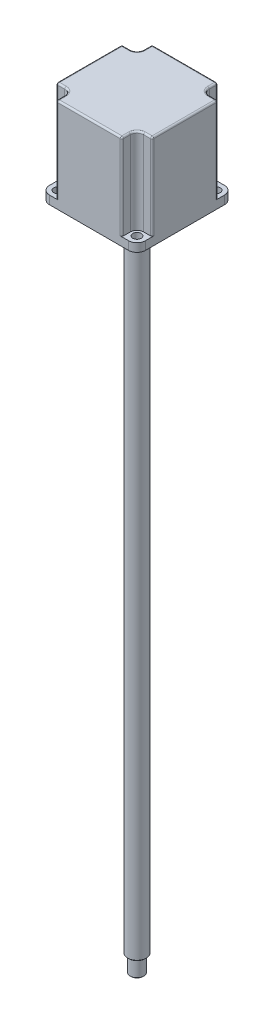
SolidWorks part; units mm, degrees
note: '?' marks a value the reader was unsure of.
material "1023 Carbon Steel Sheet (SS)"
ref_plane "Front" through (0, 0, 0) normal (0, 0, 1) x (1, 0, 0)
ref_plane "Top" through (0, 0, 0) normal (0, 1, 0) x (1, 0, 0)
ref_plane "Right" through (0, 0, 0) normal (1, 0, 0) x (0, 0, -1)
ref_axis "Axis1" through (-84.4107, 0, 0) along (1, 0, 0)?
ref_axis "Axis2" through (0, 64.3378, 0) along (0, -1, 0)?
ref_axis "Axis3" through (0, 0, -102.329) along (0, 0, 1)?
sketch "Sketch1" plane through (0, 0, 0) normal (0, 1, 0) x (1, 0, 0)
  line L1 (-28.5, -28.5) -> (28.5, -28.5)
  line L2 (-28.5, -28.5) -> (-28.5, 28.5)
  line L3 (-28.5, 28.5) -> (28.5, 28.5)
  line L4 (28.5, -28.5) -> (28.5, 28.5)
  line L5 (-28.5, -28.5) -> (28.5, 28.5) construction
  line L6 (-28.5, 28.5) -> (28.5, -28.5) construction
  point P0 (0, 0)
  dimension "D1" = 57
  dimension "D2" = 57
extrude "Extrude1" add sketch "Sketch1" along normal blind 76
hole_wizard "Ø5.0 (5) Diameter Hole1" positions "Sketch5" profile "Sketch4" hole size "Ø5.0" standard "ISO" end condition through all
sketch "Sketch5" plane through (0, 0, 0) normal (0, -1, 0) x (1, 0, 0)
  line L0 (-28.5, 28.5) -> (28.5, -28.5) construction
  line L3 (28.5, 28.5) -> (-28.5, -28.5) construction
  point P0 (-23.5, 23.5)
  point P1 (23.5, 23.5)
  point P3 (23.5, -23.5)
  point P5 (-23.5, -23.5)
  dimension "D1" = 47
  dimension "D2" = 47
sketch "Sketch4" plane through (-23.5, 0, 23.5) normal (1, 0, 0) x (0, 0, -1)
  line L0 (0, 0) -> (0, 76)
  line L1 (0, 76) -> (2.5, 76)
  line L2 (2.5, 76) -> (2.5, 0)
  line L5 (2.5, 0) -> (0, 0)
  line L11 (0, -6.35) -> (0, 107.95) construction
  dimension "Thru Hole Dia." = 5
  dimension "Thru Hole Depth" = 76
sketch "Sketch6" plane through (0, 76, 0) normal (0, 1, 0) x (1, 0, 0)
  line L0 (-19.5, 23.5) -> (-19.5, 32.5117)
  line L1 (-19.5, 32.5117) -> (-33.9089, 32.5117)
  line L2 (-33.9089, 32.5117) -> (-33.9089, 19.5)
  line L3 (-33.9089, 19.5) -> (-23.5, 19.5)
  line L4 (19.5, 23.5) -> (19.5, 36.4716)
  line L5 (19.5, 36.4716) -> (41.1684, 36.4716)
  line L6 (41.1684, 36.4716) -> (41.1684, 19.5)
  line L7 (41.1684, 19.5) -> (23.5, 19.5)
  line L8 (23.5, -19.5) -> (44.2522, -19.5)
  line L9 (44.2522, -19.5) -> (44.2522, -40.0504)
  line L10 (44.2522, -40.0504) -> (19.5, -40.0504)
  line L11 (19.5, -40.0504) -> (19.5, -23.5)
  line L12 (-23.5, -19.5) -> (-37.6708, -19.5)
  line L13 (-37.6708, -19.5) -> (-37.6708, -37.8282)
  line L14 (-37.6708, -37.8282) -> (-19.5, -37.8282)
  line L15 (-19.5, -37.8282) -> (-19.5, -23.5)
  circle A0 centre (-23.5, 23.5) radius 4
  circle A1 centre (23.5, 23.5) radius 4
  circle A2 centre (23.5, -23.5) radius 4
  circle A3 centre (-23.5, -23.5) radius 4
  circle M1 centre (-23.5, -23.5) radius 2.5
  circle M2 centre (23.5, -23.5) radius 2.5
  circle M3 centre (23.5, 23.5) radius 2.5
  circle M4 centre (-23.5, 23.5) radius 2.5
  line M5 (28.5, -28.5) -> (28.5, 28.5)
  line M6 (28.5, 28.5) -> (-28.5, 28.5)
  line M7 (-28.5, 28.5) -> (-28.5, -28.5)
  line M8 (-28.5, -28.5) -> (28.5, -28.5)
  dimension "D1" = 8
  dimension "D2" = 8
  dimension "D3" = 8
  dimension "D4" = 8
extrude "Extrude4" cut sketch "Sketch6" against normal blind 71 contours L2 L3 L0 L1 M7 M6 | A0 L0 L3 M6 M7 | A0 M4 | L7 L6 L5 L4 M6 M5 | A1 L7 L4 M5 M6 | A1 M3 | A2 M2 | A2 L11 L8 M8 M5 | L11 L10 L9 L8 M5 M8 | L14 L15 L12 L13 M8 M7 | A3 L12 L15 M7 M8 | A3 M1
fillet "Fillet1" radius 5 4 edges at (-28.5, 2.5, 28.5) (28.5, 2.5, 28.5) (28.5, 2.5, -28.5) (-28.5, 2.5, -28.5)
sketch "Sketch7" plane through (0, 76, 0) normal (0, 1, 0) x (1, 0, 0)
  circle A0 centre (0, 0) radius 3
  dimension "D1" = 6
extrude "Extrude5" add sketch "Sketch7" against normal blind 101 separate body
sketch "Sketch8" plane through (0, 0, 0) normal (0, -1, 0) x (1, 0, 0)
  circle A0 centre (0, 0) radius 19.05
  dimension "D1" = 38.1
extrude "Extrude6" add sketch "Sketch8" along normal blind 3
fillet "Fillet2" radius 1 24 edges at (-26, 76, 19.5) (-20.6716, 76, 20.6716) (-19.5, 76, 26) (0, 76, 28.5) (19.5, 76, 26) (20.6716, 76, 20.6716) (26, 76, 19.5) (28.5, 76, 0) (19.5, 76, -26) (26, 76, -19.5) (20.6716, 76, -20.6716) (-26, 76, -19.5) (-19.5, 76, -26) (-20.6716, 76, -20.6716) (0, 76, -28.5) (-28.5, 76, 0) (-19.5, 40.5, 28.5) (-28.5, 40.5, 19.5) (-28.5, 40.5, -19.5) (-19.5, 40.5, -28.5) (19.5, 40.5, -28.5) (28.5, 40.5, -19.5) (28.5, 40.5, 19.5) (19.5, 40.5, 28.5)
sketch "Sketch9" plane through (0, 0, 0) normal (0, -1, 0) x (1, 0, 0)
  circle A0 centre (0, 0) radius 5.5
  dimension "D1" = 11
extrude "Boss-Extrude1" add sketch "Sketch9" along normal blind 388
chamfer "Chamfer1" distance 0.5 angle 45 1 edges at (0, -388, -5.5)
sketch "Sketch10" plane through (0, -388, 0) normal (0, -1, 0) x (1, 0, 0)
  circle A0 centre (0, 0) radius 4
  dimension "D1" = 8
extrude "Boss-Extrude2" add sketch "Sketch10" along normal blind 10
chamfer "Chamfer2" distance 0.5 angle 45 1 edges at (0, -398, -4)
sketch "Sketch11" plane through (0, 0, 28.5) normal (0, 0, 1) x (1, 0, 0)
  line L0 (-23.5, 0) -> (23.5, 0) construction
  line L1 (-39.5371, 56) -> (41.6895, 56)
  line L2 (-39.5371, 56) -> (-39.5371, 87.8245)
  line L3 (-39.5371, 87.8245) -> (41.6895, 87.8245)
  line L4 (41.6895, 56) -> (41.6895, 87.8245)
  dimension "D1" = 56
extrude "Cut-Extrude1" cut sketch "Sketch11" against normal up to next
fillet "Fillet3" radius 1 24 edges at (19.2071, 56, 28.2071) (0, 56, 28.5) (-19.2071, 56, 28.2071) (-19.5, 56, 25.5) (-20.6716, 56, 20.6716) (-25.5, 56, 19.5) (-28.2071, 56, 19.2071) (-28.5, 56, 0) (-28.2071, 56, -19.2071) (-25.5, 56, -19.5) (-20.6716, 56, -20.6716) (-19.5, 56, -25.5) (-19.2071, 56, -28.2071) (0, 56, -28.5) (19.2071, 56, -28.2071) (19.5, 56, -25.5) (20.6716, 56, -20.6716) (25.5, 56, -19.5) (28.2071, 56, -19.2071) (28.5, 56, 0) (28.2071, 56, 19.2071) (25.5, 56, 19.5) (20.6716, 56, 20.6716) (19.5, 56, 25.5)
